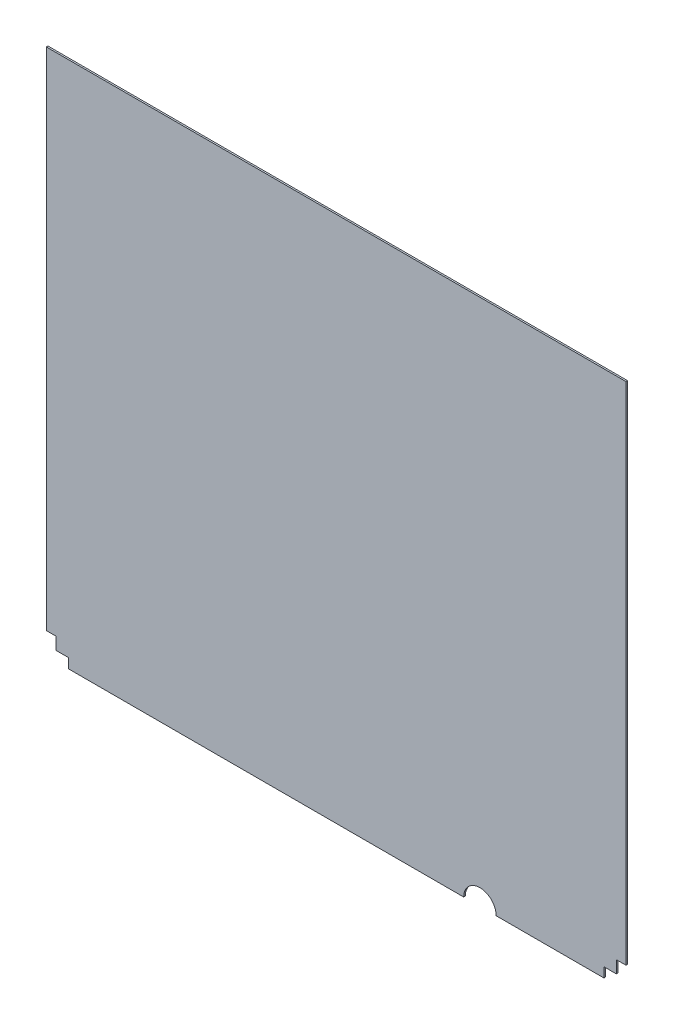
SolidWorks part; units mm, degrees
ref_plane "Front Plane" through (0, 0, 0) normal (0, 0, 1) x (1, 0, 0)
ref_plane "Top Plane" through (0, 0, 0) normal (0, 1, 0) x (1, 0, 0)
ref_plane "Right Plane" through (0, 0, 0) normal (1, 0, 0) x (0, 0, -1)
sketch "Sketch1" plane through (0, 0, 0) normal (0, 0, 1) x (1, 0, 0)
  line L0 (0, 34.544) -> (15.24, 34.544)
  line L1 (0, 0) -> (907.001, 0)
  line L2 (0, 0) -> (0, 825.5)
  line L3 (0, 825.5) -> (907.001, 825.5)
  line L4 (907.001, 0) -> (907.001, 825.5)
  line L5 (0, 0) -> (914.4, 0) construction
  line L6 (0, 0) -> (0, 914.4) construction
  line L7 (0, 914.4) -> (914.4, 914.4) construction
  line L8 (914.4, 0) -> (914.4, 914.4) construction
  line L9 (15.24, 34.544) -> (15.24, 15.24)
  line L10 (15.24, 15.24) -> (34.544, 15.24)
  line L11 (34.544, 15.24) -> (34.544, 0)
  line L12 (907.001, 34.544) -> (891.761, 34.544)
  line L13 (891.761, 34.544) -> (891.761, 15.24)
  line L14 (891.761, 15.24) -> (872.457, 15.24)
  line L15 (872.457, 15.24) -> (872.457, 0)
  arc A0 (703.801, 0) -> (653.001, 0) centre (678.401, 0) ccw
  dimension "D13" = 25.4
  dimension "D1" = 825.5
  dimension "D2" = 907.001
  dimension "D3" = 914.4
  dimension "D4" = 914.4
  dimension "D5" = 15.24
  dimension "D6" = 15.24
  dimension "D7" = 34.544
  dimension "D8" = 34.544
  dimension "D9" = 15.24
  dimension "D10" = 15.24
  dimension "D11" = 34.544
  dimension "D12" = 34.544
  dimension "D14" = 203.2
extrude "Boss-Extrude1" add sketch "Sketch1" along normal blind 2.54 contours L15 L14 L13 L12 L4 L3 L2 L0 L9 L10 L11 L1 region at (453.195, 414.1736, 0)
